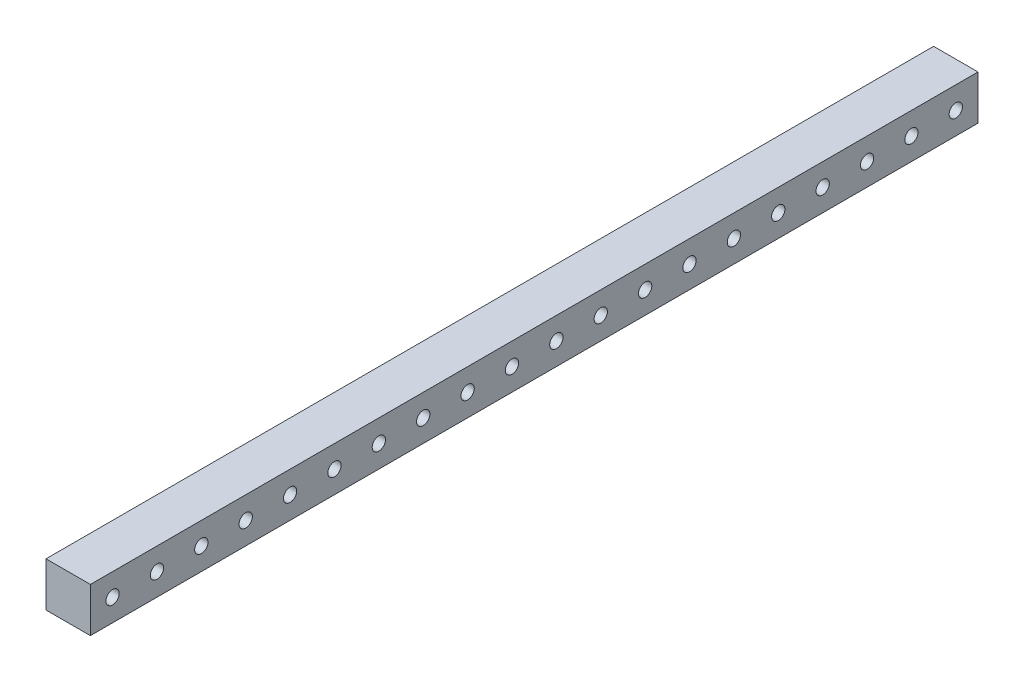
SolidWorks part; units mm, degrees
ref_plane "Front Plane" through (0, 0, 0) normal (0, 0, 1) x (1, 0, 0)
ref_plane "Top Plane" through (0, 0, 0) normal (0, 1, 0) x (1, 0, 0)
ref_plane "Right Plane" through (0, 0, 0) normal (1, 0, 0) x (0, 0, -1)
sketch "Sketch1" plane through (0, 0, 0) normal (0, 0, 1) x (1, 0, 0)
  line L0 (-10, -10) -> (10, 10) construction
  line L1 (-10, 10) -> (10, 10)
  line L2 (-10, 10) -> (-10, -10)
  line L3 (-10, -10) -> (10, -10)
  line L4 (10, 10) -> (10, -10)
  point P4 (0, 0)
  dimension "D1" = 20
  dimension "D2" = 45
extrude "Boss-Extrude1" add sketch "Sketch1" along normal blind 400
hole_wizard "Ø6.0mm Dowel Hole1" positions "Sketch2" profile "Sketch3" hole size "Ø6.0" standard "ANSI Metric" end condition through all
sketch "Sketch2" plane through (10, 0, 0) normal (1, 0, 0) x (0, 0, -1)
  line L0 (0, -10) -> (0, 10) construction
  point P0 (-10, 0)
  point P7 (0, 0)
  dimension "D1" = 10
sketch "Sketch3" plane through (10, 0, 10) normal (0, 1, 0) x (0, 0, -1)
  line L0 (0, 0) -> (0, 20)
  line L1 (0, 20) -> (3, 20)
  line L2 (3, 20) -> (3, 0)
  line L5 (3, 0) -> (0, 0)
  line L11 (0, -6.35) -> (0, 107.95) construction
  dimension "Thru Hole Dia." = 6
  dimension "Thru Hole Depth" = 20
pattern_linear "LPattern2" count 20 spacing 20 along (0, 0, 1) of "Ø6.0mm Dowel Hole1"
